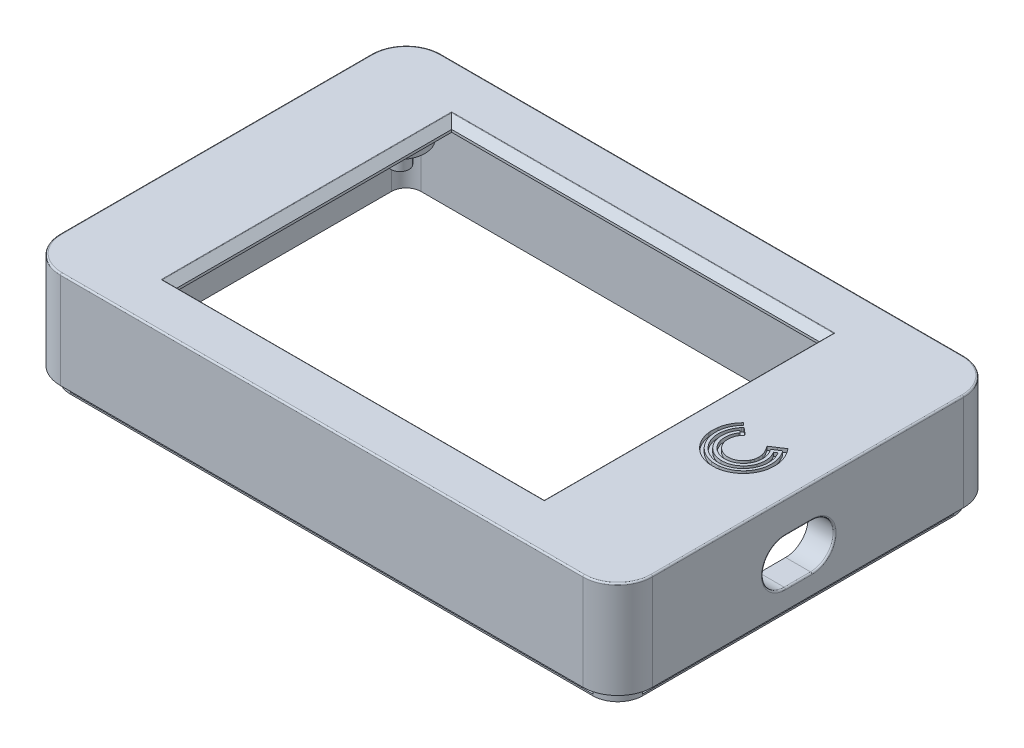
SolidWorks part; units mm, degrees
note: The reader was unsure of these and kept them because the rebuilt part matched: shared geometry of "Esquisse32<2>", "Esquisse48<2>".
other "Marquage2"
sketch "Esquisse44" plane through (-47.6, -20, 30.6) normal (-0.0394, -0.9945, 0.0967) x (-0.9946, 0.0483, 0.0914)
ref_plane "Front Plane" through (0, 0, 0) normal (0, 0, 1) x (1, 0, 0)
ref_plane "Top Plane" through (0, 0, 0) normal (0, 1, 0) x (1, 0, 0)
ref_plane "Right Plane" through (0, 0, 0) normal (1, 0, 0) x (0, 0, -1)
sketch "Esquisse1" plane through (0, 0, 0) normal (0, 1, 0) x (1, 0, 0)
  line L1 (-46, 29) -> (46, 29)
  line L2 (-46, 29) -> (-46, -29)
  line L3 (-46, -29) -> (46, -29)
  line L4 (46, 29) -> (46, -29)
  line L5 (-46, 29) -> (46, -29) construction
  line L6 (-46, -29) -> (46, 29) construction
  line L7 (-43, 25) -> (43, 25) construction
  line L8 (-43, 25) -> (-43, -25) construction
  line L9 (-31.8, -22.1) -> (27.3, -22.1)
  line L10 (-31.8, -22.1) -> (-31.8, 22.1)
  line L11 (-31.8, 22.1) -> (27.3, 22.1)
  line L12 (27.3, -22.1) -> (27.3, 22.1)
  line L13 (-31.8, -22.1) -> (27.3, 22.1) construction
  line L14 (-31.8, 22.1) -> (27.3, -22.1) construction
  line L15 (-43, -25) -> (43, -25) construction
  line L16 (43, 25) -> (43, -25) construction
  line L17 (-43, 25) -> (43, -25) construction
  line L18 (-43, -25) -> (43, 25) construction
  point P0 (0, 0)
  point P6 (0, 0)
  point P9 (-2.25, 0)
  dimension "D1" = 58
  dimension "D2" = 92
  dimension "D3" = 50
  dimension "D4" = 44.2
  dimension "D5" = 59.1
  dimension "D6" = 86
  dimension "D7" = 15.7
  dimension "D8" = 11.2
extrude "Boss.-Extru.1" add sketch "Esquisse1" along normal blind 1.6
fillet "Congé1" radius 4 4 edges at (46, 0.8, 29) (46, 0.8, -29) (-46, 0.8, 29) (-46, 0.8, -29)
chamfer "Chanfrein1" distance 1.2 angle 45 4 edges at (-2.25, 1.6, -22.1) (-31.8, 1.6, 0) (-2.25, 1.6, 22.1) (27.3, 1.6, 0)
sketch "Esquisse12" plane through (0, 0, 0) normal (0, -1, 0) x (1, 0, 0)
  line L0 (0, 0) -> (-39, 0) construction
  line L1 (-39, 21) -> (39, 21) construction
  line L2 (-39, 21) -> (-39, -21) construction
  line L3 (-39, -21) -> (39, -21) construction
  line L4 (39, 21) -> (39, -21) construction
  line L5 (-39, 21) -> (39, -21) construction
  line L6 (-39, -21) -> (39, 21) construction
  line L7 (-39, 0) -> (-45.8499, 0) construction
  circle A0 centre (-39, 21) radius 4
  circle A1 centre (-39, -21) radius 4
  circle A2 centre (39, 21) radius 4
  circle A3 centre (39, -21) radius 4
  point P0 (0, 0)
  dimension "D1" = 42
  dimension "D2" = 78
extrude "Boss.-Extru.2" add sketch "Esquisse12" along normal blind 4 contours A1 | A0 | A3 | A2
sketch "Esquisse13" plane through (0, 0, 0) normal (0, -1, 0) x (1, 0, 0)
  circle A1 centre (-39, 21) radius 1.45
  circle A2 centre (-39, -21) radius 1.45
  circle A3 centre (39, -21) radius 1.45
  circle A4 centre (39, 21) radius 1.45
extrude "Boss.-Extru.3" add sketch "Esquisse13" along normal blind 7.5
sketch "Esquisse32" plane through (0, 0, 0) normal (0, -1, 0) x (1, 0, 0)
  line L4 (46, -25) -> (46, 25)
  line L6 (46, -25) -> (46, 25)
  line L12 (42, 29) -> (-42, 29)
  line L14 (42, 29) -> (-42, 29)
  line L16 (-46, 25) -> (-46, -25)
  line L17 (-46, 25) -> (-46, -25)
  line L18 (-42, -29) -> (42, -29)
  line L19 (-42, -29) -> (42, -29)
  arc A4 (46, 25) -> (42, 29) centre (42, 25) ccw
  arc A6 (46, 25) -> (42, 29) centre (42, 25) ccw
  arc A12 (-42, 29) -> (-46, 25) centre (-42, 25) ccw
  arc A14 (-42, 29) -> (-46, 25) centre (-42, 25) ccw
  arc A16 (-46, -25) -> (-42, -29) centre (-42, -25) ccw
  arc A17 (-46, -25) -> (-42, -29) centre (-42, -25) ccw
  arc A18 (42, -29) -> (46, -25) centre (42, -25) ccw
  arc A19 (42, -29) -> (46, -25) centre (42, -25) ccw
  dimension "D1" = 0
extrude "Extru.-Mince3" add sketch "Esquisse32" along normal blind 16 thin thin type one direction reverse wall 1.6
extrude "Extru.-Mince4" add sketch "Esquisse32<2>" along normal blind 14 and the other way blind 1.6 thin
sketch "Esquisse32<2>" plane through (0, 0, 0) normal (0, -1, 0) x (1, 0, 0) same geometry as "Esquisse32"
sketch3d "Esquisse3D2"
  line L0 (-46, -14, -25) -> (-46, -16, -25) construction
  line L6 (-46, -15, -25) -> (-46, -15.75, -25)
  line L7 (-46, -15, -25) -> (-46, -14.25, -25)
  line L8 (-46, -14.25, -25) -> (-45.25, -15, -25)
  line L9 (-45.25, -15, -25) -> (-46, -15.75, -25)
extrude "Enlèv. mat.-Extru.3 ok" cut sketch "Esquisse3D2" along direction (0, 0, -1) on the side of the normal blind 50
sketch3d "Esquisse3D3"
  line L0 (46, -16, -25) -> (46, -14, -25) construction
  line L5 (46, -15, -25) -> (46, -15.75, -25)
  line L6 (46, -15, -25) -> (46, -14.25, -25)
  line L7 (46, -15.75, -25) -> (45.25, -15, -25)
  line L8 (45.25, -15, -25) -> (46, -14.25, -25)
extrude "Enlèv. mat.-Extru.4 ok" cut sketch "Esquisse3D3" along direction (0, 0, 1) on the side against the normal blind 50
sketch3d "Esquisse3D4"
  line L0 (42, -16, 29) -> (42, -14, 29) construction
  line L1 (42, -16, 27.4) -> (42, 0, 27.4) construction
  line L2 (42, -15, 29) -> (42, -14.25, 29)
  line L4 (42, -15, 29) -> (42, -14.25, 29)
  line L5 (42, -15, 29) -> (42, -15.75, 29)
  line L8 (42, -15.75, 29) -> (42, -15, 28.25)
  line L9 (42, -15, 28.25) -> (42, -14.25, 29)
extrude "Enlèv. mat.-Extru.5" cut sketch "Esquisse3D4" along direction (-1, 0, 0) on the side of the normal blind 84 contours L4 L5 L8 L9
sketch "Esquisse45" plane through (0, 1.6, 0) normal (0, 1, 0) x (1, 0, 0)
  line L2 (47.6, 0) -> (28.5, 0) construction
  line L3 (38.05, 0) -> (37.55, 0) construction
  line L4 (47.6, 25) -> (47.6, -25) construction
  line L6 (28.5, 23.3) -> (28.5, -23.3) construction
  point P0 (37.2387, 0)
  line B0 (34.2158, 2.7113) -> (34.3885, 2.9127)
  line B1 (34.3885, 2.9127) -> (34.4378, 2.8723)
  spline B2 degree 3 poles (32.2337, -0.3842) (32.2377, -0.4186) (32.2519, -0.5344) (32.264, -0.6416) knots 0 0 0 0 1 1 1 1
  spline B3 degree 3 poles (32.264, -0.6416) (32.3608, -1.4972) (32.7507, -2.4235) (33.303, -3.113) knots 1 1 1 1 2 2 2 2
  spline B4 degree 3 poles (33.303, -3.113) (33.4921, -3.3501) (33.8794, -3.7342) (34.1159, -3.9223) knots 2 2 2 2 3 3 3 3
  spline B5 degree 3 poles (34.1159, -3.9223) (34.8233, -4.4844) (35.7228, -4.8635) (36.5984, -4.9704) knots 3 3 3 3 4 4 4 4
  spline B6 degree 3 poles (36.5984, -4.9704) (36.9003, -5.0068) (37.7725, -4.9915) (38.0171, -4.946) knots 4 4 4 4 5 5 5 5
  spline B7 degree 3 poles (38.0171, -4.946) (38.532, -4.8532) (38.9035, -4.7337) (39.3593, -4.5183) knots 5 5 5 5 6 6 6 6
  spline B8 degree 3 poles (39.3593, -4.5183) (40.5052, -3.9735) (41.3817, -3.0412) (41.8615, -1.851) knots 6 6 6 6 7 7 7 7
  spline B9 degree 3 poles (41.8615, -1.851) (41.9771, -1.5647) (42.0958, -1.1348) (42.1539, -0.7967) knots 7 7 7 7 8 8 8 8
  spline B10 degree 3 poles (42.1539, -0.7967) (42.2119, -0.4607) (42.2156, 0.3707) (42.1644, 0.7032) knots 8 8 8 8 9 9 9 9
  spline B11 degree 3 poles (42.1644, 0.7032) (42.0391, 1.4819) (41.7529, 2.2231) (41.3225, 2.8733) knots 9 9 9 9 10 10 10 10
  spline B12 degree 3 poles (41.3225, 2.8733) (41.1105, 3.194) (40.8811, 3.4892) (40.8532, 3.4722) knots 10 10 10 10 11 11 11 11
  spline B13 degree 3 poles (40.8532, 3.4722) (40.8403, 3.4638) (40.3817, 3.1649) (39.835, 2.8066) knots 11 11 11 11 12 12 12 12
  spline B14 degree 3 poles (39.835, 2.8066) (39.5035, 2.5889) (39.1719, 2.3712) (38.8404, 2.1536) knots 12 12 12 12 13 13 13 13
  spline B15 degree 3 poles (38.8404, 2.1536) (38.9054, 2.0538) (38.9705, 1.9541) (39.0355, 1.8544) knots 13 13 13 13 14 14 14 14
  spline B16 degree 3 poles (39.0355, 1.8544) (39.381, 1.3248) (39.5374, 1.0087) (39.6375, 0.6245) knots 14 14 14 14 15 15 15 15
  spline B17 degree 3 poles (39.6375, 0.6245) (39.6876, 0.4377) (39.6916, 0.3863) (39.6888, -0.008) knots 15 15 15 15 16 16 16 16
  spline B18 degree 3 poles (39.6888, -0.008) (39.686, -0.4044) (39.6814, -0.4515) (39.6265, -0.6482) knots 16 16 16 16 17 17 17 17
  spline B19 degree 3 poles (39.6265, -0.6482) (39.5935, -0.7637) (39.5149, -0.9667) (39.4519, -1.097) knots 17 17 17 17 18 18 18 18
  spline B20 degree 3 poles (39.4519, -1.097) (38.7411, -2.5405) (36.904, -2.9519) (35.6554, -1.9446) knots 18 18 18 18 19 19 19 19
  spline B21 degree 3 poles (35.6554, -1.9446) (35.2612, -1.6269) (34.9623, -1.1748) (34.8242, -0.6895) knots 19 19 19 19 20 20 20 20
  spline B22 degree 3 poles (34.8242, -0.6895) (34.7448, -0.404) (34.7207, -0.1831) (34.7379, 0.1317) knots 20 20 20 20 21 21 21 21
  spline B23 degree 3 poles (34.7379, 0.1317) (34.7723, 0.7572) (34.9859, 1.2742) (35.407, 1.747) knots 21 21 21 21 22 22 22 22
  spline B24 degree 3 poles (35.407, 1.747) (35.5388, 1.8917) (35.5583, 1.9259) (35.5349, 1.9475) knots 22 22 22 22 23 23 23 23
  spline B25 degree 3 poles (35.5349, 1.9475) (35.5178, 1.9647) (35.275, 2.1679) (34.9938, 2.4034) knots 23 23 23 23 24 24 24 24
  spline B26 degree 3 poles (34.9938, 2.4034) (34.7126, 2.6389) (34.4634, 2.8485) (34.4378, 2.8723) knots 24 24 24 24 25 25 25 25
  spline B27 degree 3 poles (34.2158, 2.7113) (32.6545, 0.8902) (32.8979, -1.7703) (34.7563, -3.2073) knots 26 26 26 26 27 27 27 27
  spline B28 degree 3 poles (34.7563, -3.2073) (36.3328, -4.4248) (38.5491, -4.3067) (40.0012, -2.9264) knots 27 27 27 27 28 28 28 28
  spline B29 degree 3 poles (40.0012, -2.9264) (40.4497, -2.4988) (40.8092, -1.9419) (41.0188, -1.3519) knots 28 28 28 28 29 29 29 29
  spline B30 degree 3 poles (41.0188, -1.3519) (41.1937, -0.8539) (41.2521, -0.4579) (41.239, 0.1186) knots 29 29 29 29 30 30 30 30
  spline B31 degree 3 poles (41.239, 0.1186) (41.2292, 0.5623) (41.1819, 0.854) (41.056, 1.2448) knots 30 30 30 30 31 31 31 31
  spline B32 degree 3 poles (41.056, 1.2448) (40.9847, 1.4682) (40.687, 2.0981) (40.6463, 2.1112) knots 31 31 31 31 32 32 32 32
  spline B33 degree 3 poles (40.6463, 2.1112) (40.6292, 2.1177) (40.2679, 1.9015) (40.2119, 1.8525) knots 32 32 32 32 33 33 33 33
  spline B34 degree 3 poles (40.2119, 1.8525) (40.2075, 1.8483) (40.2561, 1.7451) (40.3216, 1.6225) knots 33 33 33 33 34 34 34 34
  spline B35 degree 3 poles (40.3216, 1.6225) (40.7763, 0.7558) (40.8507, -0.2454) (40.5271, -1.1667) knots 34 34 34 34 35 35 35 35
  spline B36 degree 3 poles (40.5271, -1.1667) (40.35, -1.669) (40.0748, -2.0977) (39.6735, -2.4956) knots 35 35 35 35 36 36 36 36
  spline B37 degree 3 poles (39.6735, -2.4956) (38.9507, -3.2105) (38.0762, -3.5515) (37.0737, -3.5081) knots 36 36 36 36 37 37 37 37
  spline B38 degree 3 poles (37.0737, -3.5081) (36.5274, -3.4849) (36.1168, -3.3771) (35.6406, -3.138) knots 37 37 37 37 38 38 38 38
  spline B39 degree 3 poles (35.6406, -3.138) (35.2904, -2.962) (35.0261, -2.7673) (34.7218, -2.4587) knots 38 38 38 38 39 39 39 39
  spline B40 degree 3 poles (34.7218, -2.4587) (34.0559, -1.7855) (33.7125, -0.941) (33.7192, 0.0125) knots 39 39 39 39 40 40 40 40
  spline B41 degree 3 poles (33.7192, 0.0125) (33.7229, 0.5374) (33.8181, 0.9696) (34.0337, 1.4609) knots 40 40 40 40 41 41 41 41
  spline B42 degree 3 poles (34.0337, 1.4609) (34.1186, 1.6532) (34.3181, 1.9946) (34.4089, 2.1054) knots 41 41 41 41 42 42 42 42
  spline B43 degree 3 poles (34.4089, 2.1054) (34.4262, 2.126) (34.4435, 2.1466) (34.4607, 2.1672) knots 42 42 42 42 43 43 43 43
  spline B44 degree 3 poles (34.4607, 2.1672) (34.5182, 2.1182) (34.5758, 2.0692) (34.6333, 2.0202) knots 43 43 43 43 44 44 44 44
  spline B45 degree 3 poles (34.6333, 2.0202) (34.7291, 1.9403) (34.8079, 1.8712) (34.8079, 1.8669) knots 44 44 44 44 45 45 45 45
  spline B46 degree 3 poles (34.8079, 1.8669) (34.8079, 1.8647) (34.7559, 1.7815) (34.6909, 1.6813) knots 45 45 45 45 46 46 46 46
  spline B47 degree 3 poles (34.6909, 1.6813) (34.2099, 0.9261) (34.0743, -0.0736) (34.3406, -0.9133) knots 46 46 46 46 47 47 47 47
  spline B48 degree 3 poles (34.3406, -0.9133) (34.5293, -1.5039) (34.9239, -2.0616) (35.4206, -2.4315) knots 47 47 47 47 48 48 48 48
  spline B49 degree 3 poles (35.4206, -2.4315) (35.6422, -2.5981) (36.0928, -2.8241) (36.3494, -2.8987) knots 48 48 48 48 49 49 49 49
  spline B50 degree 3 poles (36.3494, -2.8987) (36.6894, -2.9975) (36.912, -3.0269) (37.2914, -3.0167) knots 49 49 49 49 50 50 50 50
  spline B51 degree 3 poles (37.2914, -3.0167) (37.4821, -3.0117) (37.7051, -2.9918) (37.7952, -2.9731) knots 50 50 50 50 51 51 51 51
  spline B52 degree 3 poles (37.7952, -2.9731) (39.0034, -2.7181) (39.9053, -1.8244) (40.1731, -0.6157) knots 51 51 51 51 52 52 52 52
  spline B53 degree 3 poles (40.1731, -0.6157) (40.2351, -0.329) (40.2456, 0.2495) (40.1899, 0.552) knots 52 52 52 52 53 53 53 53
  spline B54 degree 3 poles (40.1899, 0.552) (40.1218, 0.9382) (39.9576, 1.3529) (39.6971, 1.7919) knots 53 53 53 53 54 54 54 54
  spline B55 degree 3 poles (39.6971, 1.7919) (39.6548, 1.8636) (39.6124, 1.9353) (39.5701, 2.007) knots 54 54 54 54 55 55 55 55
  spline B56 degree 3 poles (39.5701, 2.007) (39.7631, 2.1321) (39.9561, 2.2572) (40.1491, 2.3822) knots 55 55 55 55 56 56 56 56
  spline B57 degree 3 poles (40.1491, 2.3822) (40.4677, 2.59) (40.7389, 2.7595) (40.7496, 2.7594) knots 56 56 56 56 57 57 57 57
  spline B58 degree 3 poles (40.7496, 2.7594) (40.8053, 2.759) (41.1673, 2.1265) (41.3211, 1.759) knots 57 57 57 57 58 58 58 58
  spline B59 degree 3 poles (41.3211, 1.759) (41.9934, 0.1601) (41.724, -1.6015) (40.6048, -2.92) knots 58 58 58 58 59 59 59 59
  spline B60 degree 3 poles (40.6048, -2.92) (39.8853, -3.7699) (38.855, -4.3155) (37.7206, -4.4511) knots 59 59 59 59 60 60 60 60
  spline B61 degree 3 poles (37.7206, -4.4511) (37.3796, -4.4937) (36.8054, -4.479) (36.478, -4.421) knots 60 60 60 60 61 61 61 61
  spline B62 degree 3 poles (36.478, -4.421) (34.417, -4.0615) (32.8905, -2.3602) (32.7594, -0.2765) knots 61 61 61 61 62 62 62 62
  spline B63 degree 3 poles (32.7594, -0.2765) (32.6804, 0.984) (33.1131, 2.183) (33.9677, 3.0599) knots 62 62 62 62 63 63 63 63
  spline B64 degree 3 poles (33.9677, 3.0599) (34.0044, 3.0975) (34.0411, 3.1351) (34.0778, 3.1727) knots 63 63 63 63 64 64 64 64
  spline B65 degree 3 poles (34.0778, 3.1727) (34.0523, 3.1957) (34.0267, 3.2187) (34.0012, 3.2418) knots 64 64 64 64 65 65 65 65
  spline B66 degree 3 poles (34.0012, 3.2418) (33.9564, 3.2806) (33.867, 3.3584) (33.801, 3.4189) knots 65 65 65 65 66 66 66 66
  spline B67 degree 3 poles (33.801, 3.4189) (33.7598, 3.4549) (33.7186, 3.4909) (33.6775, 3.5269) knots 66 66 66 66 67 67 67 67
  spline B68 degree 3 poles (33.6775, 3.5269) (33.6321, 3.4772) (33.5868, 3.4275) (33.5414, 3.3778) knots 67 67 67 67 68 68 68 68
  spline B69 degree 3 poles (33.5414, 3.3778) (32.8635, 2.6476) (32.4439, 1.7913) (32.2827, 0.8025) knots 68 68 68 68 69 69 69 69
  spline B70 degree 3 poles (32.2827, 0.8025) (32.2491, 0.5927) (32.2133, -0.2341) (32.2337, -0.3842) knots 69 69 69 69 70 70 70 70
  line B71 (33.6775, 3.5269) -> (40.8532, 3.4722) construction
  line B72 (33.6775, 3.5269) -> (33.6242, -3.4722) construction
  line B73 (40.8532, 3.4722) -> (40.7999, -3.5269) construction
  line B74 (33.6242, -3.4722) -> (40.7999, -3.5269) construction
  line B75 (33.6775, 3.5269) -> (40.7999, -3.5269) construction
  line B76 (40.8532, 3.4722) -> (33.6242, -3.4722) construction
  dimension "D1" = 0.5
sketch_block_instance "Bloc2-1"
sketch_block "Bloc2"
sketch_block_instance "Bloc1-1"
sketch_block "Bloc1"
extrude "Enlèv. mat.-Extru.8" cut sketch "Esquisse45" against normal blind 0.6
sketch "Esquisse48" plane through (47.6, 0, 0) normal (1, 0, 0) x (0, 0, -1)
  line L0 (25, 1.6) -> (25, -14) construction
  line L1 (-25, 1.6) -> (25, 1.6) construction
  line L2 (-25, 1.6) -> (-25, -7.25) construction
  line L3 (-25, -7.25) -> (25, -7.25) construction
  line L4 (25, 1.6) -> (25, -7.25) construction
  line L5 (0, -7.25) -> (0, 1.6) construction
  line L6 (0.625, -7.25) -> (-3.625, -7.25) construction
  line L7 (0.625, -10.875) -> (-3.625, -10.875)
  line L8 (0.625, -3.625) -> (-3.625, -3.625)
  arc A0 (0.625, -10.875) -> (0.625, -3.625) centre (0.625, -7.25) ccw
  arc A1 (-3.625, -3.625) -> (-3.625, -10.875) centre (-3.625, -7.25) ccw
  point P11 (-1.5, -7.25)
  point P16 (-7.25, -7.25)
  point P17 (4.25, -7.25)
  dimension "D1" = 8.85
  dimension "D2" = 1.5
  dimension "D3" = 11.5
  dimension "D4" = 7.25
extrude "Extru.-Mince5" add sketch "Esquisse48" against normal blind 4.25 thin thin type one direction wall 1
extrude "Enlèv. mat.-Extru.11 ok" cut sketch "Esquisse48<2>" against normal blind 4
sketch "Esquisse48<2>" plane through (47.6, 0, 0) normal (1, 0, 0) x (0, 0, -1) same geometry as "Esquisse48"
sketch3d "Esquisse3D6"
  line L0 (-42, -16, -29) -> (-42, -14, -29) construction
  line L2 (-42, -15, -29) -> (-42, -15.75, -29)
  line L3 (-42, -15, -29) -> (-42, -14.25, -29)
  line L4 (-42, -16, -27.4) -> (-42, 0, -27.4) construction
  line L6 (-42, -15.75, -29) -> (-42, -15, -28.25)
  line L7 (-42, -15, -28.25) -> (-42, -14.25, -29)
extrude "Enlèv. mat.-Extru.15" cut sketch "Esquisse3D6" along direction (1, 0, 0) on the side against the normal blind 84 contours L7 L3 L2 L6
fillet "Congé2" radius 1 4 edges at (-39, 0, -17) (-39, 0, 25) (39, 0, -17) (39, 0, 25)
fillet "Congé3" radius 0.25 8 edges at (45.9598, 1.6, -28.9598) (0, 1.6, -30.6) (-45.9598, 1.6, -28.9598) (-47.6, 1.6, 0) (-45.9598, 1.6, 28.9598) (0, 1.6, 30.6) (45.9598, 1.6, 28.9598) (47.6, 1.6, 0)
fillet "Congé4" radius 0.25 4 edges at (47.6, -7.25, 7.25) (47.6, -3.625, 1.5) (47.6, -7.25, -4.25) (47.6, -10.875, 1.5)
fillet "Congé5" radius 0.125 4 edges at (-2.25, 1.6, 23.3) (28.5, 1.6, 0) (-2.25, 1.6, -23.3) (-33, 1.6, 0)
